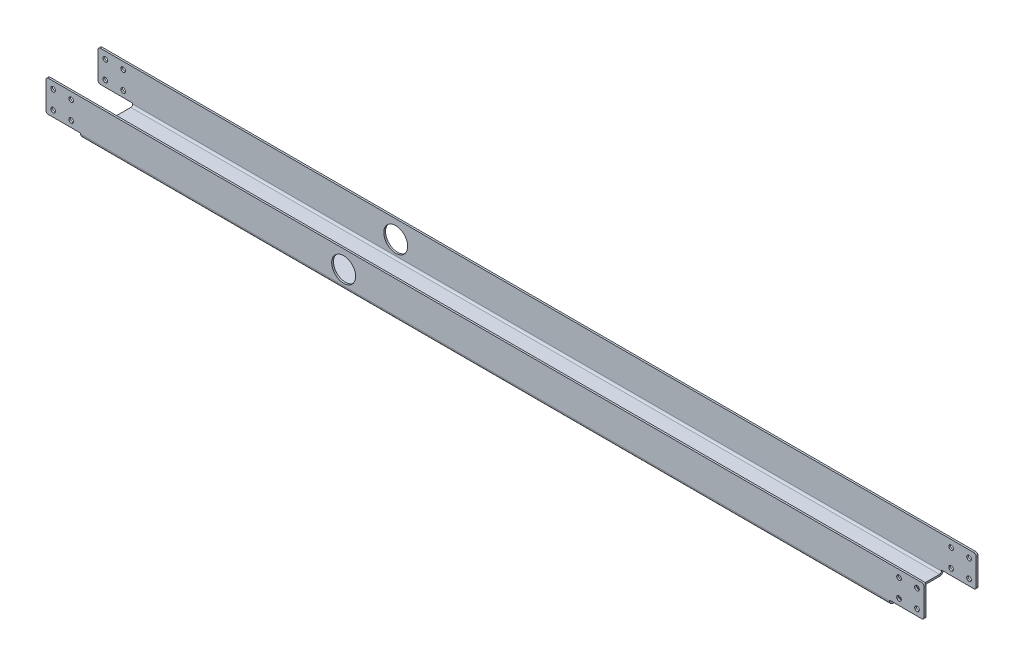
SolidWorks part; units mm, degrees
note: The reader was unsure of these and kept them because the rebuilt part matched: flange length of "Edge-Flange1", "Edge-Flange2".
ref_plane "Front Plane" through (0, 0, 0) normal (0, 0, 1) x (1, 0, 0)
ref_plane "Top Plane" through (0, 0, 0) normal (0, 1, 0) x (1, 0, 0)
ref_plane "Right Plane" through (0, 0, 0) normal (1, 0, 0) x (0, 0, -1)
sketch "Sketch1" plane through (0, 0, 0) normal (0, 1, 0) x (1, 0, 0)
  line L1 (429.26, -28.575) -> (-429.26, -28.575)
  line L2 (429.26, -28.575) -> (429.26, 28.575)
  line L3 (429.26, 28.575) -> (-429.26, 28.575)
  line L4 (-429.26, -28.575) -> (-429.26, 28.575)
  line L5 (429.26, -28.575) -> (-429.26, 28.575) construction
  line L6 (429.26, 28.575) -> (-429.26, -28.575) construction
  point P0 (0, 0)
  dimension "D1" = 858.52
  dimension "D2" = 57.15
base flange "Base-Flange1" sketch "Sketch1" thickness 1.8974 reverse thickness direction no parameters "D1"=2.032
edge flange "Edge-Flange1" sketch "Sketch8" flange angle 90 flange length 38.1 flange position material inside bend radius 2.032 thickness 1.8974 relief rectangular parameters "D6"=10
sketch "Sketch8" plane through (0, 0, 28.575) normal (0, 0, -1) x (-1, 0, 0)
  line L0 (466.09, 36.2026) -> (466.09, 2.8778)
  line L2 (-429.26, 0) -> (-429.26, 2.8778)
  line L3 (-466.09, 36.2026) -> (466.09, 36.2026)
  line L4 (429.26, 2.8778) -> (429.26, 0)
  line L5 (429.26, 0) -> (-429.26, 0) construction
  line L6 (429.26, 0) -> (-429.26, 0)
  line L7 (466.09, 2.8778) -> (429.26, 2.8778)
  line L8 (-429.26, -1.8974) -> (429.26, -1.8974) construction
  line L9 (-466.09, 36.2026) -> (-466.09, 2.8778)
  line L10 (-466.09, 2.8778) -> (-429.26, 2.8778)
  dimension "D1" = 36.83
  dimension "D2" = 4.7752
  dimension "D3" = 38.1
  dimension "D4" = 4.7752
  dimension "D5" = 36.83
bend "EdgeBend1" bend radius 2.032 bend angle 90 parameters "D5"=1
edge flange "Edge-Flange2" sketch "Sketch11" flange angle 90 flange length 38.1 flange position material inside bend radius 2.032 thickness 1.8974 relief rectangular parameters "D6"=10
sketch "Sketch11" plane through (0, 0, -28.575) normal (0, 0, 1) x (1, 0, 0)
  line L0 (466.09, 36.2026) -> (466.09, 2.8778)
  line L2 (-429.26, 0) -> (-429.26, 2.8778)
  line L3 (-466.09, 36.2026) -> (466.09, 36.2026)
  line L4 (429.26, 2.8778) -> (429.26, 0)
  line L5 (429.26, 0) -> (-429.26, 0) construction
  line L6 (429.26, 0) -> (-429.26, 0)
  line L7 (466.09, 2.8778) -> (429.26, 2.8778)
  line L8 (429.26, -1.8974) -> (-429.26, -1.8974) construction
  line L9 (-466.09, 36.2026) -> (-466.09, 2.8778)
  line L10 (-429.26, 2.8778) -> (-466.09, 2.8778)
  dimension "D1" = 36.83
  dimension "D2" = 4.7752
  dimension "D3" = 38.1
  dimension "D4" = 4.7752
  dimension "D5" = 36.83
bend "EdgeBend2" bend radius 2.032 bend angle 90 parameters "D5"=2
sketch "Sketch12" plane through (0, 0, 28.575) normal (0, 0, 1) x (1, 0, 0)
  line L0 (-429.26, 2.032) -> (-429.26, 2.8778) construction
  line L1 (-466.09, 36.2026) -> (466.09, 36.2026) construction
  line L2 (-429.26, 2.032) -> (429.26, 2.032) construction
  line L3 (-394.97, 2.032) -> (-433.07, 2.032) construction
  line L4 (-394.97, 2.032) -> (-394.97, 50.5557) construction
  line L5 (-394.97, 50.5557) -> (-433.07, 50.5557) construction
  line L6 (-433.07, 2.032) -> (-433.07, 50.5557) construction
  line L7 (-466.09, 2.8778) -> (-466.09, 36.2026) construction
  circle A0 centre (-458.47, 28.5826) radius 2.4638
  circle A1 centre (-458.47, 9.5326) radius 2.4638
  circle A2 centre (-439.42, 28.5826) radius 2.4638
  circle A3 centre (-439.42, 9.5326) radius 2.4638
  dimension "D1" = 4.9276
  dimension "D2" = 7.62
  dimension "D3" = 19.05
  dimension "D4" = 7.62
  dimension "D5" = 19.05
  dimension "D6" = 38.1
  dimension "D7" = 3.81
  dimension "D8" = 48.5237
  dimension "D9" = 88.9
extrude "Cut-Extrude1" cut sketch "Sketch12" against normal through all normal cut yes
mirror "Mirror1" about plane through (0, 0, 0) normal (1, 0, 0) of "Cut-Extrude1"
fillet "Fillet1" radius 2.54 8 edges at (466.09, 36.2026, -27.6263) (466.09, 36.2026, 27.6263) (466.09, 2.8778, 27.6263) (466.09, 2.8778, -27.6263) (-466.09, 2.8778, 27.6263) (-466.09, 2.8778, -27.6263) (-466.09, 36.2026, 27.6263) (-466.09, 36.2026, -27.6263)
sketch "Sketch13" plane through (0, 0, 28.575) normal (0, 0, 1) x (1, 0, 0)
  line L0 (429.26, -1.8974) -> (-429.26, -1.8974) construction
  line L1 (-466.09, 5.4178) -> (-466.09, 33.6626) construction
  circle A0 centre (-150.114, 17.1526) radius 12.7
  dimension "D1" = 19.05
  dimension "D3" = 25.4
  dimension "D2" = 315.976
extrude "Cut-Extrude2" cut sketch "Sketch13" against normal through all normal cut yes
sketch "Bend-Lines1" [suppressed] plane through (0, 0, 0) normal (0, 1, 0) x (1, 0, 0)
sketch "Bounding-Box1" [suppressed] plane through (0, 0, 0) normal (0, 1, 0) x (1, 0, 0)
sheet metal parameters "Sheet-Metal1" thickness 1.8974 parameters "D1"=2.032
flat pattern "Flat-Pattern1" [suppressed]
sketch "Bend-Lines2" plane through (0, 0, 0) normal (0, 1, 0) x (1, 0, 0)
sketch3d "Bounding-Box2" [suppressed]
  line L0 (-469.9, -28.575, 0) -> (469.9, -28.575, 0) construction
  line L1 (-469.9, 28.575, 0) -> (469.9, 28.575, 0) construction
  line L2 (-469.9, -28.575, 0) -> (-469.9, 28.575, 0) construction
  line L3 (469.9, -28.575, 0) -> (469.9, 28.575, 0) construction
sheet metal parameters "Sheet-Metal2" thickness 1.8974 parameters "D1"=2.032
flat pattern "Flat-Pattern1"
sketch "Bend-Lines2" plane through (0, 0, 0) normal (0, 1, 0) x (1, 0, 0)
  line L0 (-469.9, -26.9866) -> (469.9, -26.9866) construction
  line L1 (-469.9, -26.9866) -> (469.9, -26.9866) construction
sketch3d "Bounding-Box2" [suppressed]
  line L0 (469.9, -63.4983, 0) -> (-469.9, -63.4983, 0) construction
  line L1 (469.9, 28.575, 0) -> (-469.9, 28.575, 0) construction
  line L2 (469.9, -63.4983, 0) -> (469.9, 28.575, 0) construction
  line L3 (-469.9, -63.4983, 0) -> (-469.9, 28.575, 0) construction
bend of the flat pattern "Flatten-<EdgeBend1>1"
sheet metal parameters "Sheet-Metal3" thickness 1.8974 parameters "D1"=2.032
flat pattern "Flat-Pattern1"
sketch "Bend-Lines2" plane through (0, 0, 0) normal (0, 1, 0) x (1, 0, 0)
  line L0 (-466.09, -26.9866) -> (466.09, -26.9866) construction
  line L1 (-466.09, -26.9866) -> (466.09, -26.9866) construction
  line L2 (466.09, 26.9866) -> (-466.09, 26.9866) construction
  line L3 (466.09, 26.9866) -> (-466.09, 26.9866) construction
sketch3d "Bounding-Box2" [suppressed]
  line L0 (466.09, -63.4983, 0) -> (-466.09, -63.4983, 0) construction
  line L1 (466.09, 63.4983, 0) -> (-466.09, 63.4983, 0) construction
  line L2 (466.09, -63.4983, 0) -> (466.09, 63.4983, 0) construction
  line L3 (-466.09, -63.4983, 0) -> (-466.09, 63.4983, 0) construction
bend of the flat pattern "Flatten-<EdgeBend1>1"
bend of the flat pattern "Flatten-<EdgeBend2>1"
sheet metal parameters "Sheet-Metal4" thickness 1.8974 parameters "D1"=2.032
flat pattern "Flat-Pattern1"
sketch "Bend-Lines2" plane through (0, 0, 0) normal (0, 1, 0) x (1, 0, 0)
  line L0 (-466.09, -26.9866) -> (466.09, -26.9866) construction
  line L1 (-466.09, -26.9866) -> (466.09, -26.9866) construction
  line L2 (466.09, 26.9866) -> (-466.09, 26.9866) construction
  line L3 (466.09, 26.9866) -> (-466.09, 26.9866) construction
sketch3d "Bounding-Box2" [suppressed]
  line L0 (466.09, -63.4983, 0) -> (-466.09, -63.4983, 0) construction
  line L1 (466.09, 63.4983, 0) -> (-466.09, 63.4983, 0) construction
  line L2 (466.09, -63.4983, 0) -> (466.09, 63.4983, 0) construction
  line L3 (-466.09, -63.4983, 0) -> (-466.09, 63.4983, 0) construction
bend of the flat pattern "Flatten-<EdgeBend1>1"
bend of the flat pattern "Flatten-<EdgeBend2>1"
sheet metal parameters "Sheet-Metal5" thickness 1.8974 parameters "D1"=2.032
flat pattern "Flat-Pattern1"
sketch "Bend-Lines2" plane through (0, 0, 0) normal (0, 1, 0) x (1, 0, 0)
  line L0 (-429.26, -26.9866) -> (429.26, -26.9866) construction
  line L1 (-429.26, -26.9866) -> (429.26, -26.9866) construction
  line L2 (429.26, 26.9866) -> (-429.26, 26.9866) construction
  line L3 (429.26, 26.9866) -> (-429.26, 26.9866) construction
sketch3d "Bounding-Box2" [suppressed]
  line L0 (466.09, -63.4983, 0) -> (-466.09, -63.4983, 0) construction
  line L1 (466.09, 63.4983, 0) -> (-466.09, 63.4983, 0) construction
  line L2 (466.09, -63.4983, 0) -> (466.09, 63.4983, 0) construction
  line L3 (-466.09, -63.4983, 0) -> (-466.09, 63.4983, 0) construction
bend of the flat pattern "Flatten-<EdgeBend1>1"
bend of the flat pattern "Flatten-<EdgeBend2>1"
sheet metal parameters "Sheet-Metal6" thickness 1.8974 parameters "D1"=2.032
flat pattern "Flat-Pattern1"
sketch "Bend-Lines2" plane through (0, 0, 0) normal (0, 1, 0) x (1, 0, 0)
  line L0 (-429.26, -26.9866) -> (429.26, -26.9866) construction
  line L1 (-429.26, -26.9866) -> (429.26, -26.9866) construction
  line L2 (429.26, 26.9866) -> (-429.26, 26.9866) construction
  line L3 (429.26, 26.9866) -> (-429.26, 26.9866) construction
sketch3d "Bounding-Box2" [suppressed]
  line L0 (466.09, -63.4983, 0) -> (-466.09, -63.4983, 0) construction
  line L1 (466.09, 63.4983, 0) -> (-466.09, 63.4983, 0) construction
  line L2 (466.09, -63.4983, 0) -> (466.09, 63.4983, 0) construction
  line L3 (-466.09, -63.4983, 0) -> (-466.09, 63.4983, 0) construction
bend of the flat pattern "Flatten-<EdgeBend1>1"
bend of the flat pattern "Flatten-<EdgeBend2>1"
